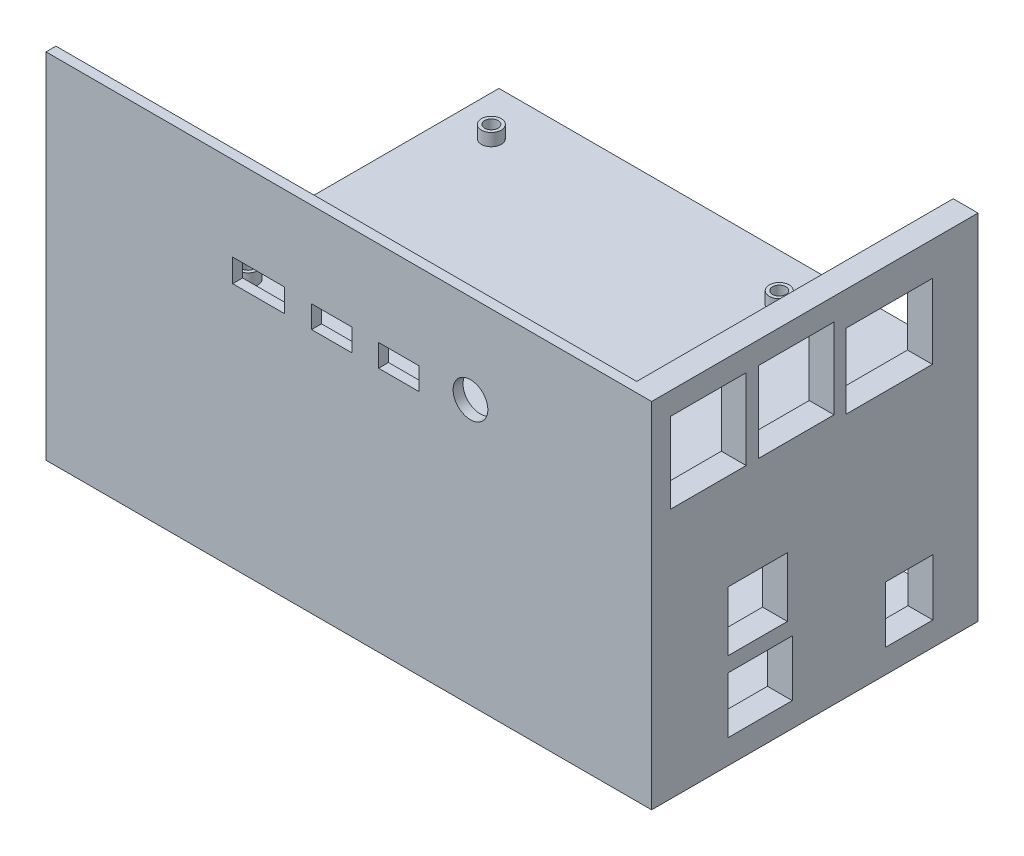
SolidWorks part; units mm, degrees
ref_plane "Front Plane" through (0, 0, 0) normal (0, 0, 1) x (1, 0, 0)
ref_plane "Top Plane" through (0, 0, 0) normal (0, 1, 0) x (1, 0, 0)
ref_plane "Right Plane" through (0, 0, 0) normal (1, 0, 0) x (0, 0, -1)
sketch "Sketch1" plane through (0, 0, 0) normal (0, 1, 0) x (1, 0, 0)
  line L0 (-46.1842, 38.8073) -> (-46.1842, 37.5573)
  line L1 (64.7734, 38.8073) -> (-62.2266, 38.8073)
  line L2 (64.7734, 38.8073) -> (64.7734, -26.1927)
  line L3 (64.7734, -26.1927) -> (-62.2266, -26.1927)
  line L4 (-62.2266, 38.8073) -> (-62.2266, -26.1927)
  line L5 (59.7734, 37.5573) -> (-57.2266, 37.5573)
  line L6 (59.7734, 37.5573) -> (59.7734, -24.9427)
  line L7 (59.7734, -24.9427) -> (-57.2266, -24.9427)
  line L8 (-57.2266, 37.5573) -> (-57.2266, -24.9427)
  line L9 (-62.2266, 31.577) -> (-57.2266, 31.577)
  circle A0 centre (-7.4728, 25.5051) radius 1.6
  circle A1 centre (-7.4728, 25.5051) radius 2.54
  circle A2 centre (-7.4728, -2.3949) radius 1.6
  circle A3 centre (-7.4728, -2.3949) radius 2.54
  circle A4 centre (43.3272, -17.5949) radius 1.6
  circle A5 centre (43.3272, -17.5949) radius 2.54
  circle A6 centre (44.4272, 30.2051) radius 1.6
  circle A7 centre (44.4272, 30.2051) radius 2.54
  dimension "D1" = 127
  dimension "D2" = 65
  dimension "D3" = 117
  dimension "D4" = 62.5
  dimension "D5" = 1.25
  dimension "D6" = 5
extrude "main body" add sketch "Sketch1" along normal blind 70 contours L4 L9 L8 L5 L0 L1 | L9 L4 L3 L2 L1 L0 L5 L6 L7 L8 region at (9.2946, 0, -38.6647) region at (-57.5103, 0, -36.0184)
sketch "Sketch6" plane through (-62.2266, 0, 0) normal (-1, 0, 0) x (0, 0, 1)
  line L0 (-6.3073, 34.968) -> (-6.3073, 70)
  line L1 (-38.8073, 70) -> (26.1927, 0) construction
  line L2 (-38.5262, 0) -> (26.4738, 65) construction
  line L3 (-38.8073, 0) -> (26.1927, 0) construction
  line L4 (-38.8073, 70) -> (26.1927, 70) construction
  circle A3 centre (-6.3073, 34.968) radius 30
  dimension "D1" = 35.032
sketch "Sketch25" plane through (-62.2266, 0, 0) normal (-1, 0, 0) x (0, 0, 1)
  line L0 (-31.3338, 70) -> (-31.3338, 60)
  line L1 (-38.8073, 70) -> (26.1927, 70) construction
  line L2 (-31.3338, 60) -> (-38.8073, 60)
  line L3 (-38.8073, 70) -> (-38.8073, 0) construction
  line L5 (-31.3338, 60) -> (18.6662, 60)
  line L6 (-31.3338, 60) -> (-31.3338, 10)
  line L7 (-31.3338, 10) -> (18.6662, 10)
  line L8 (18.6662, 60) -> (18.6662, 10)
  circle A0 centre (-31.3338, 60) radius 2.15
  circle A1 centre (-31.3338, 10) radius 2.15
  circle A2 centre (18.6662, 60) radius 2.15
  circle A3 centre (18.6662, 10) radius 2.15
  dimension "D1" = 7.4735
  dimension "D2" = 10
  dimension "D3" = 50
  dimension "D4" = 50
extrude "fan mounts" cut sketch "Sketch25" against normal blind 5 contours L0 A0 L2 | L2 A0 L6 | L6 A0 L5 | L5 A0 L0 | L7 A1 L6 | L6 A1 L7 | L7 A3 L8 | L8 A3 L7 | L8 A2 L5 | L5 A2 L8 region at (-62.2266, 60.9125, -30.4213) region at (-62.2266, 60.9125, -32.2463) region at (-62.2266, 59.0875, -32.2463) region at (-62.2266, 59.0875, -30.4213) region at (-62.2266, 60.3042, 18.9704) region at (-62.2266, 59.0875, 17.7537) region at (-62.2266, 10.9125, -30.4213) region at (-62.2266, 9.6958, -31.638) region at (-62.2266, 9.6958, 18.9704) region at (-62.2266, 10.9125, 17.7537)
extrude "fan hole" cut sketch "Sketch6" against normal blind 5 contours A3 region at (-62.2266, 14.3548, -26.9205)
sketch "Sketch7" plane through (-62.2266, 0, 0) normal (-1, 0, 0) x (0, 0, 1)
  line L1 (-38.8073, 0) -> (26.1927, 0)
  line L2 (-38.8073, 0) -> (-38.8073, -1.25)
  line L3 (-38.8073, -1.25) -> (26.1927, -1.25)
  line L4 (26.1927, 0) -> (26.1927, -1.25)
  dimension "D1" = 1.25
  dimension "D2" = 65
extrude "bottom plate" add sketch "Sketch7" against normal up to vertex (127 mm away) up to point (64.7734, 0, 26.1927)
extrude "arduino mount 1" add sketch "Sketch1<3>" along normal blind 2.5 contours A1 A0 region at (-9.9409, 0, -25.5051)
sketch "Sketch1<3>" plane through (0, 0, 0) normal (0, 1, 0) x (1, 0, 0) same geometry as "Sketch1"
extrude "arduino mount 2" add sketch "Sketch1<4>" along normal blind 2.5 contours A3 A2 region at (-9.9409, 0, 2.3949)
sketch "Sketch1<4>" plane through (0, 0, 0) normal (0, 1, 0) x (1, 0, 0) same geometry as "Sketch1"
extrude "arduino mount 3" add sketch "Sketch1<5>" along normal blind 2.5 contours A7 A6 region at (41.9591, 0, -30.2051)
sketch "Sketch1<5>" plane through (0, 0, 0) normal (0, 1, 0) x (1, 0, 0) same geometry as "Sketch1"
extrude "arduino mount 4" add sketch "Sketch1<6>" along normal blind 2.5 contours A5 A4 region at (40.8591, 0, 17.5949)
sketch "Sketch1<6>" plane through (0, 0, 0) normal (0, 1, 0) x (1, 0, 0) same geometry as "Sketch1"
sketch "Sketch9" plane through (64.7734, 0, 0) normal (1, 0, 0) x (0, 0, -1)
  line L1 (-26.1927, 70) -> (-26.1927, -1.25) construction
  line L2 (-11.5927, 11.4288) -> (0.9073, 11.4288)
  line L3 (-11.5927, 3.65) -> (-11.5927, -1.25)
  line L4 (38.8073, -1.25) -> (-26.1927, -1.25) construction
  line L5 (-11.5927, 3.65) -> (-11.5927, 14.95)
  line L6 (-26.1927, 3.65) -> (-11.5927, 3.65)
  line L11 (-11.5927, 3.65) -> (-11.5927, -1.25)
  line L12 (-11.5927, 3.65) -> (1.3923, 3.65)
  line L13 (-11.5927, 3.65) -> (-11.5927, 14.95)
  line L14 (-11.5927, 14.95) -> (1.3923, 14.95)
  line L15 (1.3923, 3.65) -> (1.3923, 14.95)
  dimension "D2" = 12.5
  dimension "D4" = 11.3
  dimension "D5" = 4.9
  dimension "D6" = 14.6
extrude "arduino usb b" cut sketch "Sketch9" against normal blind 5 contours L5 region at (64.7734, 9.3, 5.1002)
sketch "Sketch12" plane through (64.7734, 0, 0) normal (1, 0, 0) x (0, 0, -1)
  line L0 (29.7073, 3.55) -> (20.2073, 3.55)
  line L1 (38.8073, 70) -> (38.8073, -1.25) construction
  line L2 (20.2073, 3.55) -> (20.2073, 14.95)
  line L3 (38.8073, -1.25) -> (-26.1927, -1.25) construction
  line L6 (38.8073, 3.55) -> (29.7073, 3.55)
  line L11 (29.7073, 3.55) -> (29.7073, -1.25)
  line L12 (20.2073, 14.95) -> (29.7073, 14.95)
  line L13 (20.2073, 14.95) -> (20.2073, 3.55)
  line L14 (20.2073, 3.55) -> (29.7073, 3.55)
  line L15 (29.7073, 14.95) -> (29.7073, 3.55)
  dimension "D1" = 11.4
  dimension "D2" = 9.5
  dimension "D5" = 4.8
  dimension "D6" = 9.1
sketch "clearance" plane through (0, 0, -37.5573) normal (0, 0, 1) x (1, 0, 0)
  line L0 (21.7529, 0) -> (21.7529, 43)
  line L1 (59.7734, 0) -> (-57.2266, 0) construction
  line L2 (59.7734, 43) -> (-30.2266, 43)
  line L3 (59.7734, 70) -> (59.7734, 0) construction
  line L5 (-30.2266, 43) -> (59.7734, 43)
  line L6 (-30.2266, 43) -> (-30.2266, 45)
  line L7 (-30.2266, 45) -> (59.7734, 45)
  line L8 (59.7734, 43) -> (59.7734, 45)
  line M3 (59.7734, 0) -> (59.7734, 70)
  dimension "D1" = 90
  dimension "D2" = 43
  dimension "D3" = 2
sketch "Sketch14" plane through (64.7734, 0, 0) normal (1, 0, 0) x (0, 0, -1)
  line L0 (29.6073, 70) -> (29.6073, 63.2)
  line L1 (38.8073, 70) -> (-26.1927, 70) construction
  line L2 (29.6073, 63.2) -> (38.8073, 63.2)
  line L3 (38.8073, 70) -> (38.8073, -1.25) construction
  line L4 (29.6073, 63.2) -> (29.6073, 48.2)
  line L5 (29.6073, 48.2) -> (12.2573, 48.2)
  line L7 (29.6073, 63.2) -> (12.2573, 63.2)
  line L8 (29.6073, 63.2) -> (29.6073, 48.2)
  line L9 (29.6073, 48.2) -> (12.2573, 48.2)
  line L10 (12.2573, 63.2) -> (12.2573, 48.2)
  dimension "D1" = 6.8
  dimension "D2" = 9.2
  dimension "D3" = 15
  dimension "D4" = 17.35
extrude "arduion power hole" cut sketch "Sketch12" against normal blind 5 contours L15 L12 L2 L0 region at (64.7734, 9.25, -24.9573)
sketch "Sketch28" plane through (64.7734, 0, 0) normal (1, 0, 0) x (0, 0, -1)
  line L0 (-11.5927, 14.95) -> (-11.5927, 17.95)
  line L2 (-11.5927, 17.95) -> (0.4073, 17.95)
  line L3 (-11.5927, 17.95) -> (-11.5927, 29.95)
  line L4 (-11.5927, 29.95) -> (0.4073, 29.95)
  line L5 (0.4073, 17.95) -> (0.4073, 29.95)
  dimension "D1" = 3
  dimension "D2" = 12
  dimension "D3" = 12
extrude "reader coax" cut sketch "Sketch28" against normal blind 5 contours L2 L5 L4 L3 region at (64.7734, 23.95, 5.5927)
extrude "separating plate" add sketch "clearance" along normal blind 62.5 contours L7 L6 L2 M3 region at (14.7734, 44, -37.5573)
sketch "Sketch24" plane through (0, 45, 0) normal (0, 1, 0) x (1, 0, 0)
  line L0 (-22.2189, 37.5573) -> (-22.2189, 27.7614)
  line L1 (-30.2266, 37.5573) -> (59.7734, 37.5573) construction
  line L2 (-22.2189, 27.7614) -> (-30.2266, 27.7614)
  line L3 (-30.2266, -24.9427) -> (-30.2266, 37.5573) construction
  line L5 (-22.2189, 27.7614) -> (35.7811, 27.7614)
  line L6 (-22.2189, 27.7614) -> (-22.2189, -21.2386)
  line L7 (-22.2189, -21.2386) -> (35.7811, -21.2386)
  line L8 (35.7811, 27.7614) -> (35.7811, -21.2386)
  circle A0 centre (-22.2189, 27.7614) radius 1.35
  circle A1 centre (-22.2189, 27.7614) radius 2
  circle A2 centre (-22.2189, -21.2386) radius 1.35
  circle A3 centre (-22.2189, -21.2386) radius 2
  circle A4 centre (35.7811, 27.7614) radius 1.35
  circle A5 centre (35.7811, 27.7614) radius 2
  circle A6 centre (35.7811, -21.2386) radius 1.35
  circle A7 centre (35.7811, -21.2386) radius 2
  dimension "D1" = 9.7959
  dimension "D2" = 8.0077
  dimension "D3" = 49
  dimension "D4" = 58
extrude "pi seats" add sketch "Sketch24" along normal blind 2.5 contours L0 A1 L2 A0 | L5 A1 L0 A0 | L6 A1 L5 A0 | L2 A1 L6 A0 | L6 A3 L7 A2 | L7 A3 L6 A2 | L8 A5 L5 A4 | L5 A5 L8 A4 | L8 A7 L7 A6 | L7 A7 L8 A6 region at (-21.1392, 45, -28.8411) region at (-23.2987, 45, -28.8411) region at (-21.1392, 45, -26.6817) region at (-23.2987, 45, -26.6817) region at (35.7811, 45, -29.7048) region at (34.7013, 45, -26.6817) region at (-21.1392, 45, 20.1589) region at (-22.2755, 45, 19.5636) region at (37.1553, 45, 19.8644) region at (34.7013, 45, 20.1589)
extrude "pi ethernet" cut sketch "Sketch14" against normal blind 5 contours L7 L10 L5 L4 region at (64.7734, 55.7, -20.9323)
sketch "Sketch16" plane through (64.7734, 0, 0) normal (1, 0, 0) x (0, 0, -1)
  line L0 (9.8073, 70) -> (9.8073, 65.5)
  line L1 (38.8073, 70) -> (-26.1927, 70) construction
  line L2 (9.8073, 65.5) -> (38.8073, 65.5)
  line L3 (38.8073, 70) -> (38.8073, -1.25) construction
  line L4 (9.8073, 65.5) -> (9.8073, 49.3)
  line L5 (9.8073, 49.3) -> (-5.3927, 49.3)
  line L7 (9.8073, 65.5) -> (-5.3927, 65.5)
  line L8 (9.8073, 65.5) -> (9.8073, 49.3)
  line L9 (9.8073, 49.3) -> (-5.3927, 49.3)
  line L10 (-5.3927, 65.5) -> (-5.3927, 49.3)
  dimension "D1" = 4.5
  dimension "D2" = 29
  dimension "D3" = 15.2
  dimension "D4" = 16.2
extrude "pi usb 3.0" cut sketch "Sketch16" against normal blind 5 contours L7 L10 L5 L4 region at (64.7734, 57.4, -2.2073)
sketch "Sketch18" plane through (64.7734, 0, 0) normal (1, 0, 0) x (0, 0, -1)
  line L0 (-5.3927, 65.5) -> (-7.8927, 65.5)
  line L1 (-5.3927, 65.5) -> (-5.3927, 49.3) construction
  line L2 (-7.8927, 65.5) -> (-7.8927, 70)
  line L3 (38.8073, 70) -> (-26.1927, 70) construction
  line L4 (-7.8927, 65.5) -> (-7.8927, 49.3)
  line L5 (-7.8927, 49.3) -> (-23.0927, 49.3)
  line L7 (-7.8927, 65.5) -> (-23.0927, 65.5)
  line L8 (-7.8927, 65.5) -> (-7.8927, 49.3)
  line L9 (-7.8927, 49.3) -> (-23.0927, 49.3)
  line L10 (-23.0927, 65.5) -> (-23.0927, 49.3)
  dimension "D1" = 2.5
  dimension "D2" = 4.5
  dimension "D3" = 16.2
  dimension "D4" = 15.2
extrude "pi usb 2.0" cut sketch "Sketch18" against normal blind 5 contours L7 L10 L5 L4 region at (64.7734, 57.4, 15.4927)
sketch "Sketch19" plane through (0, 0, 26.1927) normal (0, 0, 1) x (1, 0, 0)
  line L0 (28.2811, 52.0684) -> (28.2811, 70)
  line L2 (28.2811, 52.0684) -> (64.7734, 52.0684)
  line L3 (64.7734, 70) -> (64.7734, -1.25) construction
  line L4 (64.7734, 70) -> (-62.2266, 70) construction
  circle A0 centre (28.2811, 52.0684) radius 3.5
  dimension "D3" = 7
  dimension "D1" = 17.9316
  dimension "D2" = 36.4923
extrude "pi audio port" cut sketch "Sketch19" against normal blind 2 contours L2 A0 | A0 L2 region at (27.7859, 51.5732, 26.1927) region at (29.7665, 53.5538, 26.1927)
sketch "Sketch20" plane through (0, 0, 26.1927) normal (0, 0, 1) x (1, 0, 0)
  line L0 (17.8734, 70) -> (17.8734, 52.8)
  line L1 (64.7734, 70) -> (-62.2266, 70) construction
  line L2 (17.8734, 52.8) -> (64.7734, 52.8)
  line L3 (64.7734, 70) -> (64.7734, -1.25) construction
  line L5 (17.8734, 52.8) -> (9.7734, 52.8)
  line L6 (17.8734, 52.8) -> (17.8734, 48.3)
  line L7 (17.8734, 48.3) -> (9.7734, 48.3)
  line L8 (9.7734, 52.8) -> (9.7734, 48.3)
  dimension "D1" = 46.9
  dimension "D2" = 17.2
  dimension "D3" = 4.5
  dimension "D4" = 8.1
extrude "pi micro hdmi right" cut sketch "Sketch20" against normal blind 2 contours L5 L8 L7 L6 region at (13.8234, 50.55, 26.1927)
sketch "Sketch21" plane through (0, 0, 26.1927) normal (0, 0, 1) x (1, 0, 0)
  line L0 (9.7734, 52.8) -> (4.3734, 52.8)
  line L1 (4.3734, 52.8) -> (4.3734, 70)
  line L4 (4.3734, 52.8) -> (-3.7266, 52.8)
  line L5 (4.3734, 52.8) -> (4.3734, 48.3)
  line L6 (4.3734, 48.3) -> (-3.7266, 48.3)
  line L7 (-3.7266, 52.8) -> (-3.7266, 48.3)
  dimension "D1" = 5.4
  dimension "D2" = 17.2
  dimension "D3" = 8.1
  dimension "D4" = 4.5
extrude "pi micro hdmi left" cut sketch "Sketch21" against normal blind 2 contours L4 L7 L6 L5 region at (0.3234, 50.55, 26.1927)
sketch "Sketch22" plane through (0, 0, 26.1927) normal (0, 0, 1) x (1, 0, 0)
  line L0 (-9.2266, 70) -> (-9.2266, 53)
  line L1 (64.7734, 70) -> (-62.2266, 70) construction
  line L2 (-9.2266, 53) -> (64.7734, 53)
  line L3 (64.7734, 70) -> (64.7734, -1.25) construction
  line L5 (-9.2266, 53) -> (-19.6266, 53)
  line L6 (-9.2266, 53) -> (-9.2266, 48.35)
  line L7 (-9.2266, 48.35) -> (-19.6266, 48.35)
  line L8 (-19.6266, 53) -> (-19.6266, 48.35)
  dimension "D1" = 74
  dimension "D2" = 17
  dimension "D3" = 10.4
  dimension "D4" = 4.65
extrude "pi usb c" cut sketch "Sketch22" against normal blind 2 contours L5 L8 L7 L6 region at (-14.4266, 50.675, 26.1927)
sketch "Sketch26" plane through (0, 0, -38.8073) normal (0, 0, -1) x (-1, 0, 0)
  line L0 (-64.7734, 70) -> (62.2266, 70) construction
  line L1 (-59.7734, 70) -> (57.2266, 70)
  line L2 (-59.7734, 70) -> (-59.7734, 0)
  line L3 (-59.7734, 0) -> (57.2266, 0)
  line L4 (57.2266, 70) -> (57.2266, 0)
  line L5 (-64.7734, 52.3621) -> (-59.7734, 52.3621)
  line L6 (-64.7734, 70) -> (-64.7734, -1.25) construction
  line L7 (57.2266, 48.248) -> (62.2266, 48.248)
  line L8 (62.2266, 70) -> (62.2266, -1.25) construction
  line L9 (-23.8806, -1.25) -> (-23.8806, 0)
  line L10 (-64.7734, -1.25) -> (62.2266, -1.25) construction
  line M11 (62.2266, 70) -> (-64.7734, 70)
  dimension "D1" = 5
  dimension "D2" = 5
  dimension "D3" = 1.25
extrude "side panel out" cut sketch "Sketch26" against normal blind 1.5 contours L4 L2 L3 M11 region at (1.2734, 35, -38.8073)
sketch "Sketch27" plane through (0, 0, 26.1927) normal (0, 0, 1) x (1, 0, 0)
  line L4 (-62.2266, 70) -> (-62.2266, -1.25)
  line L5 (-62.2266, -1.25) -> (64.7734, -1.25)
  line L6 (64.7734, -1.25) -> (64.7734, 70)
  line L7 (64.7734, 70) -> (-62.2266, 70)
  line L8 (-62.2266, 70) -> (-62.2266, -1.25)
  line L9 (-62.2266, -1.25) -> (64.7734, -1.25)
  line L10 (64.7734, -1.25) -> (64.7734, 70)
  line L11 (64.7734, 70) -> (-62.2266, 70)
  line L12 (17.8734, 52.8) -> (9.7734, 52.8)
  line L13 (17.8734, 48.3) -> (17.8734, 52.8)
  line L14 (9.7734, 48.3) -> (17.8734, 48.3)
  line L15 (9.7734, 52.8) -> (9.7734, 48.3)
  line L16 (17.8734, 52.8) -> (9.7734, 52.8)
  line L17 (17.8734, 48.3) -> (17.8734, 52.8)
  line L18 (9.7734, 48.3) -> (17.8734, 48.3)
  line L19 (9.7734, 52.8) -> (9.7734, 48.3)
  line L20 (4.3734, 52.8) -> (-3.7266, 52.8)
  line L21 (4.3734, 48.3) -> (4.3734, 52.8)
  line L22 (-3.7266, 48.3) -> (4.3734, 48.3)
  line L23 (-3.7266, 52.8) -> (-3.7266, 48.3)
  line L24 (4.3734, 52.8) -> (-3.7266, 52.8)
  line L25 (4.3734, 48.3) -> (4.3734, 52.8)
  line L26 (-3.7266, 48.3) -> (4.3734, 48.3)
  line L27 (-3.7266, 52.8) -> (-3.7266, 48.3)
  line L28 (-9.2266, 53) -> (-19.6266, 53)
  line L29 (-9.2266, 48.35) -> (-9.2266, 53)
  line L30 (-19.6266, 48.35) -> (-9.2266, 48.35)
  line L31 (-19.6266, 53) -> (-19.6266, 48.35)
  line L32 (-9.2266, 53) -> (-19.6266, 53)
  line L33 (-9.2266, 48.35) -> (-9.2266, 53)
  line L34 (-19.6266, 48.35) -> (-9.2266, 48.35)
  line L35 (-19.6266, 53) -> (-19.6266, 48.35)
  circle A1 centre (28.2811, 52.0684) radius 3.5
  circle A2 centre (28.2811, 52.0684) radius 3.5
  dimension "D1" = 0
  dimension "D2" = 0
  dimension "D3" = 0
  dimension "D4" = 0
  dimension "D5" = 0
extrude "making i/o panel thicker" add sketch "Sketch27" along normal blind 0.75
sketch "Sketch30" plane through (64.7734, 0, 0) normal (1, 0, 0) x (0, 0, -1)
  line L0 (38.8073, 70) -> (38.8073, -1.25) construction
  line L1 (-26.9427, 70) -> (38.8073, 70)
  line L2 (-26.9427, 70) -> (-26.9427, 43)
  line L3 (-26.9427, 43) -> (38.8073, 43)
  line L4 (38.8073, 70) -> (38.8073, 43)
  dimension "D1" = 27
extrude "bottom half" [suppressed] cut sketch "Sketch30" against normal up to vertex
sketch "Sketch34" plane through (64.7734, 0, 0) normal (1, 0, 0) x (0, 0, -1)
  line L0 (38.8073, 70) -> (38.8073, -1.25) construction
  line L1 (-26.9427, -1.25) -> (38.8073, -1.25)
  line L2 (-26.9427, -1.25) -> (-26.9427, 43)
  line L3 (-26.9427, 43) -> (38.8073, 43)
  line L4 (38.8073, -1.25) -> (38.8073, 43)
  dimension "D1" = 44.25
extrude "top half" [suppressed] cut sketch "Sketch34" against normal up to vertex
sketch "Sketch35" plane through (0, 70, 0) normal (0, 1, 0) x (1, 0, 0)
  line L1 (-62.2266, -26.9427) -> (-57.2266, -26.9427)
  line L2 (-62.2266, -26.9427) -> (-62.2266, 38.8073)
  line L3 (-62.2266, 38.8073) -> (-57.2266, 38.8073)
  line L4 (-57.2266, -26.9427) -> (-57.2266, 38.8073)
extrude "remove fan" cut sketch "Sketch35" against normal up to vertex (71.25 mm away) up to point (-62.2266, -1.25, -38.8073)
sketch "Sketch36" plane through (0, 70, 0) normal (0, 1, 0) x (1, 0, 0)
  line L1 (64.7734, -26.9427) -> (-57.2266, -26.9427)
  line L2 (64.7734, -26.9427) -> (64.7734, 38.8073)
  line L3 (64.7734, 38.8073) -> (-57.2266, 38.8073)
  line L4 (-57.2266, -26.9427) -> (-57.2266, 38.8073)
extrude "just fan" [suppressed] cut sketch "Sketch36" against normal up to vertex
